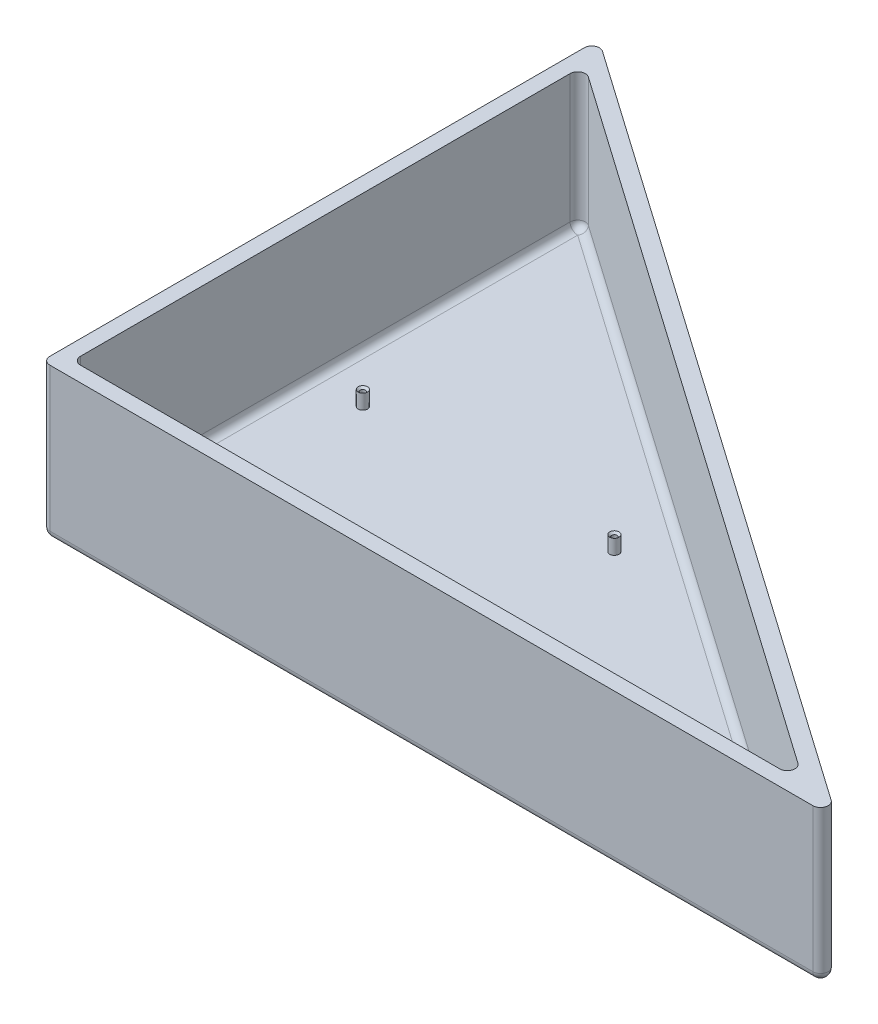
SolidWorks part; units mm, degrees
ref_plane "Front Plane" through (0, 0, 0) normal (0, 0, 1) x (1, 0, 0)
ref_plane "Top Plane" through (0, 0, 0) normal (0, 1, 0) x (1, 0, 0)
ref_plane "Right Plane" through (0, 0, 0) normal (1, 0, 0) x (0, 0, -1)
sketch "Sketch1" plane through (0, 0, 0) normal (0, 1, 0) x (1, 0, 0)
  line L0 (-57.785, 122.4592) -> (-57.785, -47.625)
  line L1 (-45.085, 34.925) -> (45.085, 34.925)
  line L2 (-45.085, 34.925) -> (-45.085, -34.925)
  line L3 (-45.085, -34.925) -> (45.085, -34.925)
  line L4 (45.085, 34.925) -> (45.085, -34.925)
  line L5 (-57.785, -47.625) -> (185.1204, -47.625)
  line L6 (185.1204, -47.625) -> (-57.785, 122.4592)
  line L7 (-62.865, 132.2178) -> (-62.865, -52.705)
  line L8 (-62.865, -52.705) -> (201.2321, -52.705)
  line L9 (201.2321, -52.705) -> (-62.865, 132.2178)
  circle A0 centre (-41.656, 32.6136) radius 1.5494
  circle A1 centre (41.8846, 32.639) radius 1.5494
  circle A2 centre (41.7068, -32.3596) radius 1.5494
  circle A3 centre (-41.6052, -32.4104) radius 1.5494
  point P5 (-45.085, 0)
  point P7 (0, 34.925)
  point P21 (440.8213, -52.705)
  point P22 (402.2348, -47.625)
  point P23 (0, 0)
  point P24 (357.0185, -47.625)
  point P25 (0, 0)
  dimension "D7" = 2.3114
  dimension "D8" = 3.0988
  dimension "D1" = 90.17
  dimension "D2" = 69.85
  dimension "D3" = 12.7
  dimension "D4" = 12.7
  dimension "D5" = 55
  dimension "D6" = 12.7
  dimension "D9" = 3.429
  dimension "D10" = 2.286
  dimension "D11" = 3.2004
  dimension "D12" = 2.5654
  dimension "D13" = 3.3782
  dimension "D14" = 3.4798
  dimension "D15" = 2.5146
  dimension "D16" = 5.08
extrude "Boss-Extrude1" add sketch "Sketch1" along normal blind 45.212 contours L8 L9 L7 L6 L5 L0 region at (67.3343, 0, -37.1154)
extrude "Boss-Extrude2" add sketch "Sketch1<3>" against normal blind 5.08 contours L8 L9 L7 L6 L5 L0 | L5 L6 L0 L1 L4 L3 L2 | A1 | A3 | L4 L1 L2 L3 A3 A2 A1 A0 | A2 | A0 region at (61.9669, 0, -34.988) region at (-0.0004, 0, 0.0006) region at (67.3343, 0, -37.1154) region at (-41.656, 0, -32.6136) region at (41.8846, 0, -32.639) region at (41.7068, 0, 32.3596) region at (-41.6052, 0, 32.4104)
sketch "Sketch1<3>" plane through (0, 0, 0) normal (0, 1, 0) x (1, 0, 0) same geometry as "Sketch1"
extrude "Boss-Extrude3" add sketch "Sketch1<4>" along normal blind 5.08 contours A1 | A2 | A3 | A0 region at (41.8846, 0, -32.639) region at (41.7068, 0, 32.3596) region at (-41.6052, 0, 32.4104)
sketch "Sketch1<4>" plane through (0, 0, 0) normal (0, 1, 0) x (1, 0, 0) same geometry as "Sketch1"
fillet "Fillet1" radius 2.54 6 edges at (-62.865, 20.066, -132.2178) (201.2321, 20.066, 52.705) (-62.865, 20.066, 52.705) (-57.785, 22.606, 47.625) (185.1204, 22.606, 47.625) (-57.785, 22.606, -122.4592)
hole_wizard "#2-56 Tapped Hole1" positions "Sketch2" profile "Sketch3" tap size "#2-56" standard "ANSI Inch"
sketch "Sketch2" plane through (0, 5.08, 0) normal (0, 1, 0) x (1, 0, 0)
  point P0 (41.8846, 32.639)
  point P3 (-41.656, 32.6136)
  point P6 (41.7068, -32.3596)
  point P9 (-41.656, -32.3596)
sketch "Sketch3" plane through (41.8846, 5.08, -32.639) normal (1, 0, 0) x (0, 0, 1)
  line L0 (0, 0) -> (0, 6.1222)
  line L1 (0, 6.1222) -> (0.889, 5.588)
  line L2 (0.889, 5.588) -> (0.889, 0.8382)
  line L3 (0.889, 0.8382) -> (1.7272, 0)
  line L5 (1.7272, 0) -> (0, 0)
  line L6 (-0.889, 0.8382) -> (-1.7272, 0) construction
  line L10 (0, 6.1222) -> (-0.889, 5.588) construction
  line L11 (0, -6.35) -> (0, 107.95) construction
  dimension "Tap Drill Dia." = 1.778
  dimension "Tap Drill Depth" = 5.588
  dimension "Near C'Sink Dia." = 3.4544
  dimension "Near C'Sink Angle" = 90
  dimension "Drill Angle" = 118
cosmetic thread "Hole Thread1" parameters "D1"=4.318, "D2"=2.1844
cosmetic thread "Hole Thread2" parameters "D1"=4.318, "D2"=2.1844
cosmetic thread "Hole Thread3" parameters "D1"=4.318, "D2"=2.1844
cosmetic thread "Hole Thread4" parameters "D1"=4.318, "D2"=2.1844
fillet "Fillet3" radius 2.54 6 edges at (-61.4978, -5.08, -129.5915) (195.5987, -5.08, 50.9288) (-62.1211, -5.08, 51.9611) (67.8825, -5.08, -40.6674) (66.4256, -5.08, 52.705) (-62.865, -5.08, -38.5867)
fillet "Fillet4" radius 2.54 6 edges at (179.487, 0, 45.8488) (-57.0411, 0, 46.8811) (-56.4178, 0, -119.8329) (-57.785, 0, -36.2474) (60.9098, 0, 47.625) (62.3667, 0, -38.3281)
